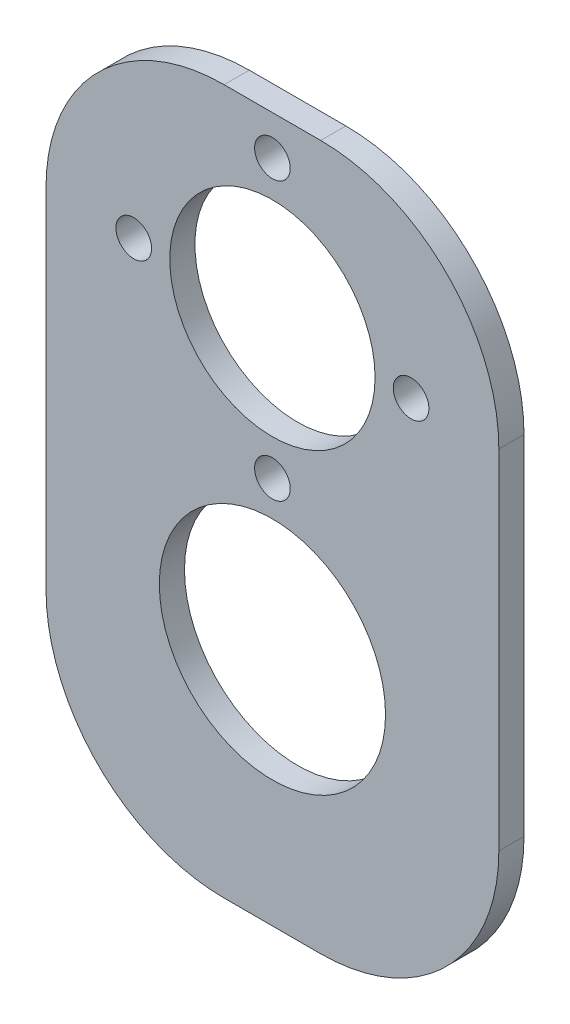
SolidWorks part; units mm, degrees
ref_plane "Front Plane" through (0, 0, 0) normal (0, 0, 1) x (1, 0, 0)
ref_plane "Top Plane" through (0, 0, 0) normal (0, 1, 0) x (1, 0, 0)
ref_plane "Right Plane" through (0, 0, 0) normal (1, 0, 0) x (0, 0, -1)
sketch "Sketch1" plane through (0, 0, 0) normal (0, 0, 1) x (1, 0, 0)
  line L0 (28.575, -34.4358) -> (-28.575, -34.4358)
  line L1 (-28.575, 54.4642) -> (28.575, 54.4642)
  line L2 (-28.575, 54.4642) -> (-28.575, -34.4358)
  line L3 (-28.575, -34.4358) -> (-28.3009, -34.7981)
  line L4 (28.575, 54.4642) -> (28.575, -34.4358)
  circle A0 centre (0, 31.9852) radius 12.954
  circle A1 centre (0, 49.4858) radius 2.25
  circle A2 centre (17.5006, 31.9852) radius 2.25
  circle A3 centre (0, 14.4846) radius 2.25
  circle A4 centre (-17.5006, 31.9852) radius 2.25
  circle A5 centre (0, -4.2098) radius 14.2748
  point P20 (0, 31.9852)
  dimension "D5" = 28.575
  dimension "D6" = 28.575
  dimension "D13" = 22.479
  dimension "D3" = 88.9
  dimension "D9" = 11.0744
  dimension "D10" = 4.9784
  dimension "D18" = 4.5
  dimension "D19" = 25.908
  dimension "D15" = 4.5
  dimension "D16" = 4.5
  dimension "D17" = 4.5
  dimension "D22" = 28.5496
  dimension "D2" = 57.15
  dimension "D7" = 28.575
  dimension "D8" = 46.0756
  dimension "D11" = 22.479
  dimension "D12" = 22.479
  dimension "D14" = 39.9796
  dimension "D20" = 28.575
  dimension "D21" = 58.674
extrude "Boss-Extrude1" add sketch "Sketch1" along normal blind 3.175 contours L4 L1 L2 L0 A5 A4 A3 A2 A1 A0 region at (0, -33.379, 0)
fillet "Fillet1" radius 22.479 4 edges at (28.575, -34.4358, 1.5875) (-28.575, -34.4358, 1.5875) (28.575, 54.4642, 1.5875) (-28.575, 54.4642, 1.5875)
